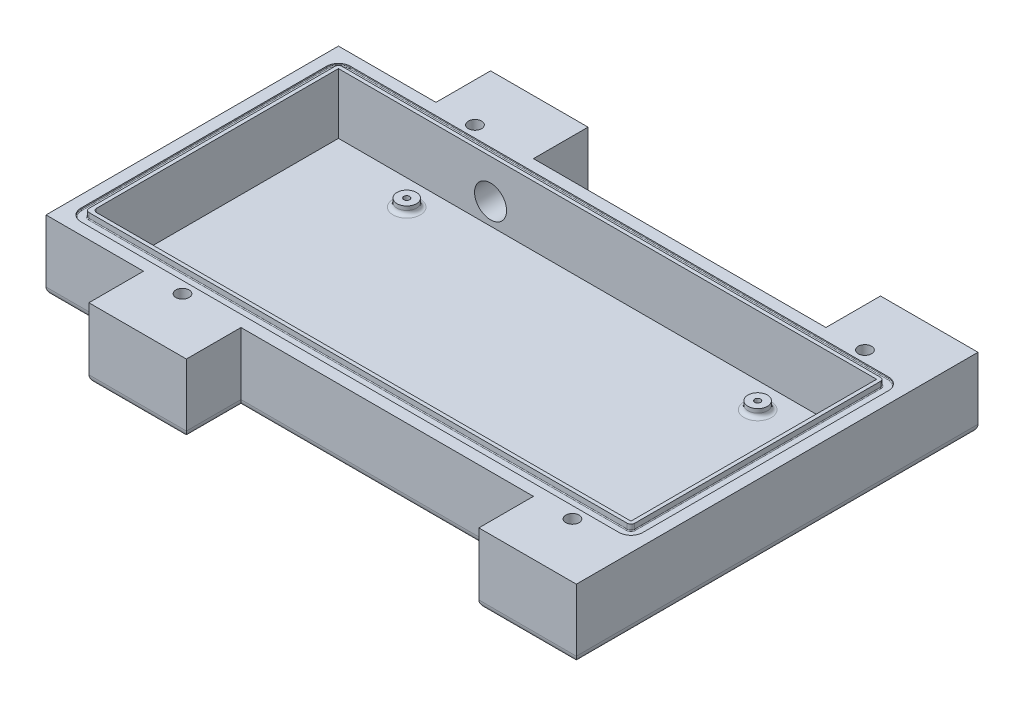
SolidWorks part; units mm, degrees
ref_plane "Front Plane" through (0, 0, 0) normal (0, 0, 1) x (1, 0, 0)
ref_plane "Top Plane" through (0, 0, 0) normal (0, 1, 0) x (1, 0, 0)
ref_plane "Right Plane" through (0, 0, 0) normal (1, 0, 0) x (0, 0, -1)
sketch "Sketch1" plane through (0, 0, 0) normal (0, 1, 0) x (1, 0, 0)
  line L1 (0, 0) -> (150, 0)
  line L2 (0, 0) -> (0, 75)
  line L3 (0, 75) -> (150, 75)
  line L4 (150, 0) -> (150, 75)
  dimension "D1" = 150
  dimension "D2" = 75
extrude "Boss-Extrude1" add sketch "Sketch1" along normal blind 18
sketch "Sketch5" plane through (0, 18, 0) normal (0, 1, 0) x (1, 0, 0)
  line L11 (6, 69) -> (6, 6)
  line L12 (6, 6) -> (144, 6)
  line L13 (144, 6) -> (144, 69)
  line L14 (144, 69) -> (6, 69)
  line L15 (6, 69) -> (6, 6)
  line L16 (6, 6) -> (144, 6)
  line L17 (144, 6) -> (144, 69)
  line L18 (144, 69) -> (6, 69)
  dimension "D1" = 6
extrude "Cut-Extrude2" cut sketch "Sketch5" against normal blind 14.5
ref_plane "Plane1" through (0, 0, -37.5) normal (0, 0, -1) x (-1, 0, 0)
ref_plane "Plane3" through (0, 9, 0) normal (0, -1, 0) x (-1, 0, 0)
sketch "Sketch2" plane through (0, 0, 0) normal (0, 0, 1) x (1, 0, 0)
  line L0 (0, 18) -> (150, 18) construction
  line L1 (150, 0) -> (125, 0)
  line L2 (150, 0) -> (150, 18)
  line L3 (150, 18) -> (125, 18)
  line L4 (125, 0) -> (125, 18)
  line L5 (0, 0) -> (150, 0) construction
  line L6 (50, 0) -> (25, 0)
  line L7 (50, 0) -> (50, 18)
  line L8 (50, 18) -> (25, 18)
  line L9 (25, 0) -> (25, 18)
  line L10 (0, 18) -> (0, 0) construction
  dimension "D1" = 25
  dimension "D2" = 25
  dimension "D3" = 25
extrude "Boss-Extrude2" add sketch "Sketch2" along normal blind 14
sketch "Sketch3" plane through (25, 0, 0) normal (-1, 0, 0) x (0, 0, 1)
  line L0 (0, 0) -> (14, 18) construction
  circle A0 centre (7, 9) radius 4.1
  point P4 (7, 9)
  dimension "D1" = 8.2
sketch "Sketch6" plane through (0, 9, 0) normal (0, 1, 0) x (1, 0, 0)
  line L0 (25, -14) -> (25, 0) construction
  line L1 (50, -14) -> (50, 0) construction
  line L2 (50, -14) -> (25, -14) construction
  line L3 (25, -14) -> (25, 0) construction
  line L4 (50, -14) -> (50, 0) construction
  line L5 (50, -14) -> (25, -14) construction
  line L6 (25, -7) -> (45, -7) construction
  line L7 (45, -7) -> (45, 6) construction
  line L8 (25, -7) -> (40, -7)
  line L9 (45, -2) -> (45, 6)
  arc A0 (40, -7) -> (45, -2) centre (40, -2) ccw
  point P6 (40, -7)
  dimension "D1" = 5
  dimension "D2" = 5
  dimension "D3" = 8
sweep "Cut-Sweep1" cut profiles "Sketch3" path "Sketch6"
sketch "Sketch7" plane through (125, 0, 0) normal (-1, 0, 0) x (0, 0, 1)
  line L0 (0, 0) -> (14, 18) construction
  circle A0 centre (7, 9) radius 4.1
  point P4 (7, 9)
  dimension "D1" = 8.2
sketch "Sketch8" plane through (0, 9, 0) normal (0, 1, 0) x (1, 0, 0)
  line L0 (150, -14) -> (150, 75) construction
  line L1 (150, -14) -> (125, -14) construction
  line L2 (125, -14) -> (125, 0) construction
  line L3 (150, -14) -> (150, 75) construction
  line L4 (150, -14) -> (125, -14) construction
  line L5 (125, -14) -> (125, 0) construction
  line L6 (125, -7) -> (145, -7) construction
  line L7 (145, -7) -> (145, 6) construction
  line L8 (125, -7) -> (140, -7)
  line L9 (145, -2) -> (145, 6)
  arc A0 (140, -7) -> (145, -2) centre (140, -2) ccw
  point P6 (140, -7)
  point P8 (145, -2)
  dimension "D1" = 5
  dimension "D2" = 5
  dimension "D3" = 5
  dimension "D4" = 13
sweep "Cut-Sweep2" cut profiles "Sketch7" path "Sketch8"
chamfer "Chamfer3" distance 2 angle 80 1 edges at (144, 9, -6) first distance on face at (146.55, 9, -6)
mirror "Mirror1" about plane through (0, 0, -37.5) normal (0, 0, -1) of "Boss-Extrude2", "Cut-Sweep1", "Cut-Sweep2"
sketch "Sketch10" plane through (0, 18, 0) normal (0, 1, 0) x (1, 0, 0)
  line L30 (4, 4) -> (146, 4)
  line L31 (4, 71) -> (4, 4)
  line L32 (146, 71) -> (4, 71)
  line L33 (146, 4) -> (146, 71)
  line L34 (6, 4) -> (144, 4)
  line L35 (4, 69) -> (4, 6)
  line L36 (144, 71) -> (6, 71)
  line L37 (146, 6) -> (146, 69)
  arc A0 (144, 4) -> (146, 6) centre (144, 6) ccw
  arc A1 (144, 71) -> (146, 69) centre (144, 69) cw
  arc A2 (4, 69) -> (6, 71) centre (6, 69) cw
  arc A3 (6, 4) -> (4, 6) centre (6, 6) cw
  dimension "D2" = 2
  dimension "D1" = 2
sketch "Sketch11" plane through (0, 0, -37.5) normal (0, 0, -1) x (-1, 0, 0)
  line L1 (-144, 18) -> (-146, 18) construction
  line L2 (-144, 18) -> (-146, 18) construction
  line L4 (-146.85, 17.5) -> (-145.15, 17.5)
  line L5 (-147.05, 17.7) -> (-147.05, 18.5)
  line L6 (-147.05, 18.5) -> (-144.95, 18.5)
  line L7 (-144.95, 17.7) -> (-144.95, 18.5)
  line L8 (-147.05, 17.5) -> (-144.95, 18.5) construction
  line L9 (-147.05, 18.5) -> (-144.95, 17.5) construction
  arc A0 (-145.15, 17.5) -> (-144.95, 17.7) centre (-145.15, 17.7) ccw
  arc A1 (-146.85, 17.5) -> (-147.05, 17.7) centre (-146.85, 17.7) cw
  dimension "D1" = 1
  dimension "D3" = 0.2
  dimension "D2" = 2.1
sweep "Cut-Sweep3" cut profiles "Sketch11" path "Sketch10"
fillet "Fillet3" radius 2 16 edges at (25, 0, -82) (37.5, 0, -89) (50, 0, -82) (137.5, 0, -89) (150, 0, -37.5) (137.5, 0, 14) (50, 0, 7) (37.5, 0, 14) (25, 0, 7) (0, 0, -37.5)
chamfer "Chamfer4" distance 2 angle 80 1 edges at (144, 9, -69) first distance on face at (146.55, 9, -69)
ref_plane "Plane2" through (6, 3.5, -6) normal (0, 0, 1) x (1, 0, 0)
sketch "Sketch13" plane through (0, 18, 0) normal (0, 1, 0) x (1, 0, 0)
  line L0 (25, 0) -> (50, 0)
  line L1 (125, 0) -> (150, 0) construction
  line L2 (150, -14) -> (150, 89) construction
  line L3 (125, 75) -> (150, 75) construction
  line L4 (25, 75) -> (50, 75) construction
  point P17 (35, 75)
  point P18 (135, 75)
  point P19 (35, 0)
  point P20 (135, 0)
  dimension "D1" = 10
  dimension "D2" = 10
hole_wizard "CBORE for M3 Hex Head Cap Screw1" positions "Sketch18" profile "Sketch16" counterbore size "M3" standard "ISO" end condition through all
sketch "Sketch18" plane through (0, 0, 0) normal (0, -1, 0) x (-1, 0, 0)
  point P0 (-35, 0)
  point P3 (-35, 75)
  point P6 (-135, 75)
  point P9 (-135, 0)
sketch "Sketch16" plane through (35, 0, 0) normal (1, 0, 0) x (0, 0, -1)
  line L0 (0, 0) -> (0, 18.0001)
  line L1 (0, 18.0001) -> (1.7, 18.0001)
  line L3 (1.7, 18.0001) -> (1.7, 2)
  line L4 (1.7, 2) -> (4.6755, 2)
  line L5 (4.6755, 2) -> (4.6755, 0)
  line L7 (4.6755, 0) -> (0, 0)
  line L11 (0, -6.35) -> (0, 107.95) construction
  dimension "Thru Hole Dia." = 3.4
  dimension "Thru Hole Depth" = 18.0001
  dimension "C'Bore Dia." = 9.351
  dimension "C'Bore Depth" = 2
sketch "Sketch19" plane through (0, 18, 0) normal (0, 1, 0) x (1, 0, 0)
  line L0 (6, 6) -> (144, 6) construction
  line L1 (6, 6) -> (144, 6)
  line L2 (144, 6) -> (144, 69) construction
  line L3 (6, 69) -> (6, 6) construction
  line L4 (144, 69.95) -> (6, 69.95)
  line L5 (5.05, 69) -> (5.05, 6)
  line L6 (6, 5.05) -> (144, 5.05)
  line L7 (144.95, 6) -> (144.95, 69)
  line L8 (144, 69.95) -> (6, 69.95)
  line L9 (5.05, 69) -> (5.05, 6)
  line L10 (6, 5.05) -> (144, 5.05)
  line L11 (144.95, 6) -> (144.95, 69)
  line L12 (144, 69) -> (6, 69) construction
  line L13 (144, 6) -> (144, 69)
  line L14 (6, 69) -> (6, 6)
  line L15 (144, 69) -> (6, 69)
  arc A4 (144.95, 69) -> (144, 69.95) centre (144, 69) ccw
  arc A5 (6, 69.95) -> (5.05, 69) centre (6, 69) ccw
  arc A6 (5.05, 6) -> (6, 5.05) centre (6, 6) ccw
  arc A7 (144, 5.05) -> (144.95, 6) centre (144, 6) ccw
  arc A8 (144.95, 69) -> (144, 69.95) centre (144, 69) ccw
  arc A9 (6, 69.95) -> (5.05, 69) centre (6, 69) ccw
  arc A10 (5.05, 6) -> (6, 5.05) centre (6, 6) ccw
  arc A11 (144, 5.05) -> (144.95, 6) centre (144, 6) ccw
  dimension "D1" = 0
extrude "Boss-Extrude3" add sketch "Sketch19" along normal blind 1
sketch "Sketch20" plane through (0, 3.5, 0) normal (0, 1, 0) x (1, 0, 0)
  circle A0 centre (120, 62.5) radius 2.5
  circle A1 centre (120, 12.5) radius 2.5
  circle A2 centre (30, 12.5) radius 2.5
  circle A3 centre (30, 62.5) radius 2.5
  circle A4 centre (120, 62.5) radius 0.75
  circle A5 centre (120, 12.5) radius 0.75
  circle A6 centre (30, 12.5) radius 0.75
  circle A7 centre (30, 62.5) radius 0.75
  point P0 (30, 62.5)
  point P1 (120, 62.5)
  point P3 (120, 12.5)
  point P5 (30, 12.5)
  dimension "D1" = 1.5
  dimension "D2" = 1.5
  dimension "D3" = 1.5
  dimension "D4" = 1.5
extrude "Boss-Extrude4" add sketch "Sketch20" along normal blind 2
fillet "Fillet4" radius 1 5 edges at (30, 3.5, -60) (120, 3.5, -60) (30, 3.5, -10) (120, 3.5, -10) (6, 11.25, -6)
